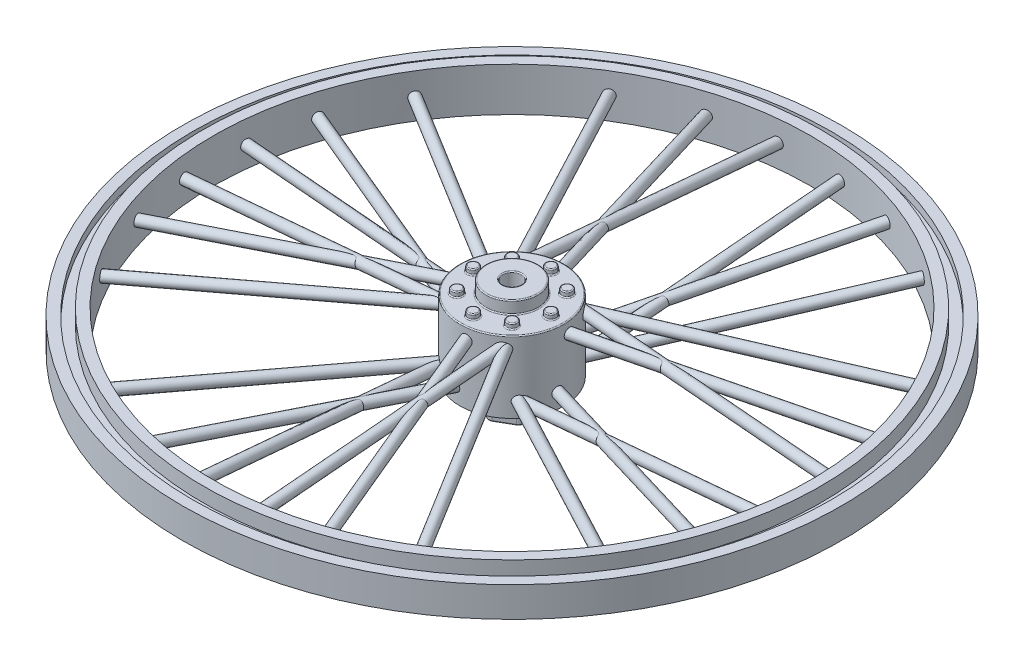
SolidWorks part; units mm, degrees
material "6061-T6 (SS)"
ref_plane "Front Plane" through (0, 0, 0) normal (0, 0, 1) x (1, 0, 0)
ref_plane "Top Plane" through (0, 0, 0) normal (0, 1, 0) x (1, 0, 0)
ref_plane "Right Plane" through (0, 0, 0) normal (1, 0, 0) x (0, 0, -1)
sketch "Sketch1" plane through (0, 0, 0) normal (1, 0, 0) x (0, 0, -1)
  line L0 (0, 0) -> (31.75, 0) construction
  line L1 (0, 0) -> (0, 21.0135) construction
  line L2 (30.75, 1.45) -> (31.75, 1.45)
  line L3 (30.75, 1.45) -> (30.75, 0.7)
  line L4 (30.75, -1.45) -> (31.75, -1.45)
  line L5 (31.75, 1.45) -> (31.75, -1.45)
  line L6 (30.75, -0.7) -> (30.75, -1.45)
  line L7 (29.75, 0.7) -> (30.75, 0.7)
  line L9 (29.75, -0.7) -> (30.75, -0.7)
  line L14 (28.75, 2.1) -> (29.75, 2.1)
  line L15 (28.75, 2.1) -> (28.75, -2.1)
  line L16 (28.75, -2.1) -> (29.75, -2.1)
  line L18 (29.75, 2.1) -> (29.75, 0.7)
  line L19 (29.75, -0.7) -> (29.75, -2.1)
  line L20 (30.25, 0.7) -> (30.25, -0.7) construction
  point P14 (30.25, 0)
  point P16 (31.75, 0)
  dimension "D1" = 63.5
  dimension "D3" = 2.9
  dimension "D4" = 4.2
  dimension "D5" = 1.4
  dimension "D6" = 1
revolve "Revolve2" add sketch "Sketch1" angle 360 about L1
sketch "Sketch2" plane through (0, 0, 0) normal (0, 1, 0) x (1, 0, 0)
  circle A0 centre (0, 0) radius 5
  dimension "D1" = 10
extrude "Boss-Extrude1" add sketch "Sketch2" along normal blind 6.9 from offset 3.6 separate body offset against normal yes
ref_axis "Axis1" through (0, 6.7291, 0) along (0, -1, 0)
ref_plane "Plane1" through (0, 0, 0) normal (0.866, 0, 0.5) x (0.5, 0, -0.866)
ref_plane "STRAIGHT" through (3, 0, 0) normal (1, 0, 0) x (0, 0, -1)
ref_axis "Axis2" through (3, -5.5, 0) along (0, 1, 0)
sketch "Sketch3" plane through (3, 0, 0) normal (1, 0, 0) x (0, 0, -1)
  line L0 (-29.5984, 0) -> (0, 2.5895)
  line L1 (-29.5984, 0) -> (-12.1475, 0) construction
  line L2 (0, 0) -> (0, 2.5895) construction
  line L5 (-29.5984, 0) -> (-29.5984, 2.1) construction
  line L6 (28.75, 2.1) -> (-28.75, 2.1) construction
  dimension "D1" = 5
  dimension "29.5" = 29.5984
sweep "Sweep1" add path "Sketch3" circular profile diameter 1 parameters "D3"=1
ref_plane "ref x1" through (2.6491, 0, -0.9642) normal (-0.9397, 0, 0.342) x (0.342, 0, 0.9397)
ref_plane "offset ref x1" through (-1.1097, 0, 0.4039) normal (-0.9397, 0, 0.342) x (0.342, 0, 0.9397)
sketch "Sketch4" plane through (-1.1097, 0, 0.4039) normal (-0.9397, 0, 0.342) x (0.342, 0, 0.9397)
  line L0 (29.7266, 0) -> (0, 2.6007)
  line L1 (29.7266, 0) -> (16.1941, 0) construction
  line L2 (29.7266, 0) -> (29.7266, 2.1) construction
  line L3 (0, 0) -> (0, 2.6007) construction
  line L4 (28.75, 2.1) -> (-28.75, 2.1) construction
  dimension "D1" = 5
sweep "Sweep2" add path "Sketch4" circular profile diameter 1 parameters "D3"=1
ref_plane "ref y1" through (2.25, 0, -1.299) normal (0.866, 0, -0.5) x (-0.5, 0, -0.866)
ref_plane "offset ref y1" through (0.7345, 0, -0.424) normal (0.866, 0, -0.5) x (-0.5, 0, -0.866)
sketch "Sketch5" plane through (0.7345, 0, -0.424) normal (0.866, 0, -0.5) x (-0.5, 0, -0.866)
  line L0 (-29.7379, 0) -> (-29.7379, 2.1) construction
  line L1 (0, 2.6017) -> (0, 0) construction
  line L2 (-29.7379, 0) -> (-18.3884, 0) construction
  line L7 (-29.7379, 0) -> (0, 2.6017)
  dimension "D1" = 5
sweep "Sweep3" add path "Sketch5" circular profile diameter 1 parameters "D3"=1
sketch "Sketch6" plane through (3, 0, 0) normal (1, 0, 0) x (0, 0, -1)
  line L0 (0, -2.5895) -> (29.5984, 0)
  line L1 (29.5984, 0) -> (0, 0) construction
  line L2 (0, -2.5895) -> (0, 0) construction
  line L3 (29.5984, 0) -> (29.5984, 2.1) construction
  line L4 (28.75, 2.1) -> (-28.75, 2.1) construction
  dimension "D1" = 5
sweep "Sweep4" add path "Sketch6" circular profile diameter 1 parameters "D3"=1
ref_plane "ref x2" through (2.6491, 0, 0.9642) normal (0.9397, 0, 0.342) x (0.342, 0, -0.9397)
ref_plane "offset ref x2" through (-1.1097, 0, -0.4039) normal (0.9397, 0, 0.342) x (0.342, 0, -0.9397)
sketch "Sketch7" plane through (-1.1097, 0, -0.4039) normal (0.9397, 0, 0.342) x (0.342, 0, -0.9397)
  line L0 (29.7266, 0) -> (0, -2.6007)
  line L1 (0, -2.6007) -> (0, 0) construction
  line L3 (19.3488, 0) -> (29.7266, 0) construction
  line L4 (29.7266, 0) -> (29.7266, 2.1) construction
  dimension "D1" = 5
sweep "Sweep5" add path "Sketch7" circular profile diameter 1 parameters "D3"=1
ref_plane "ref y2" through (2.25, 0, 1.299) normal (-0.866, 0, -0.5) x (-0.5, 0, 0.866)
ref_plane "offset ref y2" through (0.7345, 0, 0.424) normal (-0.866, 0, -0.5) x (-0.5, 0, 0.866)
sketch "Sketch8" plane through (0.7345, 0, 0.424) normal (-0.866, 0, -0.5) x (-0.5, 0, 0.866)
  line L0 (-29.7379, 0) -> (0, -2.6017)
  line L1 (0, -2.6017) -> (0, 0) construction
  line L2 (-17.5286, 0) -> (-29.7379, 0) construction
  line L3 (-29.7379, 0) -> (-29.7379, 2.1) construction
  dimension "D1" = 5
sweep "Sweep6" add path "Sketch8" circular profile diameter 1 parameters "D3"=1
pattern_circular "CirPattern1" count 4 over 360 about axis through (0, 3.3, 0) along (0, 1, 0) of "Sweep2", "Sweep3", "Sweep1", "Sweep4", "Sweep5", "Sweep6"
sketch "Sketch9" plane through (0, -3.6, 0) normal (0, -1, 0) x (1, 0, 0)
  line L5 (-3.9291, 0.75) -> (-2, 0.75)
  line L12 (-2, -0.75) -> (-3.9291, -0.75)
  line L13 (3.9291, -0.75) -> (2, -0.75)
  line L15 (2, 0.75) -> (3.9291, 0.75)
  line L16 (-2, 0.75) -> (-2, -0.75)
  line L17 (2, -0.75) -> (2, 0.75)
  line L24 (2, 0) -> (-2, 0) construction
  arc A0 (-3.9291, 0.75) -> (3.9291, 0.75) centre (0, 0) cw
  arc A1 (-3.9291, -0.75) -> (3.9291, -0.75) centre (0, 0) ccw
  point P12 (0, 0)
  dimension "D1" = 4
  dimension "D3" = 4
  dimension "D2" = 1.5
extrude "Cut-Extrude1" cut sketch "Sketch9" against normal blind 5
sketch "Sketch10" plane through (0, 1.4, 0) normal (0, -1, 0) x (1, 0, 0)
  line L0 (-2, 0.75) -> (-2, -0.75) construction
  line L1 (-2, 1.1547) -> (-2, -1.1547)
  line L2 (-2, -1.1547) -> (0, -2.3094)
  line L3 (0, -2.3094) -> (2, -1.1547)
  line L4 (2, -1.1547) -> (2, 1.1547)
  line L5 (2, 1.1547) -> (0, 2.3094)
  line L6 (0, 2.3094) -> (-2, 1.1547)
  circle A0 centre (0, 0) radius 2 construction
  dimension "D1" = 4
extrude "Boss-Extrude2" add sketch "Sketch10" along normal offset from surface (7.6 mm away) 2.6 up to face at (0, -3.6, 0) offset beyond the face yes
sketch "Sketch11" plane through (0, 3.3, 0) normal (0, 1, 0) x (1, 0, 0)
  circle A0 centre (0, 0) radius 2.5
  dimension "D1" = 5
extrude "Boss-Extrude3" add sketch "Sketch11" along normal blind 1.2
sketch "Sketch12" plane through (0, 4.5, 0) normal (0, 1, 0) x (1, 0, 0)
  circle A0 centre (0, 0) radius 0.9
  dimension "D1" = 1.8
extrude "Cut-Extrude2" cut sketch "Sketch12" against normal through all
sketch "Sketch13" plane through (0, 3.3, 0) normal (0, 1, 0) x (1, 0, 0)
  line L0 (-5, 0) -> (-2.5, 0) construction
  circle A0 centre (-3.75, 0) radius 0.5
  circle A1 centre (0, 0) radius 5 construction
  circle A2 centre (0, 0) radius 2.5 construction
  point P3 (-3.75, 0)
  dimension "D1" = 1
extrude "Boss-Extrude4" add sketch "Sketch13" along normal blind 0.5
fillet "Fillet2" radius 0.1 11 edges at (0, 4.5, 2.5) (0, 3.3, 2.5) (-1, -6.2, 1.7321) (1, -6.2, 1.7321) (2, -6.2, 0) (1, -6.2, -1.7321) (-1, -6.2, -1.7321) (-2, -6.2, 0) (0, -6.2, 0.9) (0, 4.5, 0.9) (0, 3.3, 5)
fillet "Fillet3" radius 0.1 2 edges at (-3.75, 3.3, 0.5) (-3.75, 3.8, 0.5)
pattern_circular "CirPattern3" count 8 over 360 about axis through (0, 3.2, 0) along (0, -1, 0) of "Boss-Extrude4", "Fillet3"
fillet "Fillet4" radius 0.5 12 edges at (1.9707, -6.1707, 1.1378) (0, -6.1707, 2.2756) (-1.9707, -6.1707, 1.1378) (-1.9707, -6.1707, -1.1378) (0, -6.1707, -2.2756) (1.9707, -6.1707, -1.1378) (2, -2.35, -1.1547) (0, -2.35, -2.3094) (-2, -2.35, -1.1547) (-2, -2.35, 1.1547) (0, -2.35, 2.3094) (2, -2.35, 1.1547)
equation "\"spk\"= 5"
equation "\"D1@Sketch3\"=\"spk\""
equation "\"D1@Sketch4\"=\"spk\""
equation "\"D1@Sketch6\" = \"spk\""
equation "\"x_angle\"= 160"
equation "\"D1@ref x1\" = \"x_angle\""
equation "\"D1@ref x2\" = 180 - \"x_angle\""
equation "\"D1@Sketch7\" = \"spk\""
equation "\"D1@Sketch5\"=\"spk\""
equation "\"D1@ref y1\"= \"y_angle\""
equation "\"y_angle\"= 30"
equation "\"D1@ref y2\"= 180 - \"y_angle\""
equation "\"D1@Sketch8\" = \"spk\""
